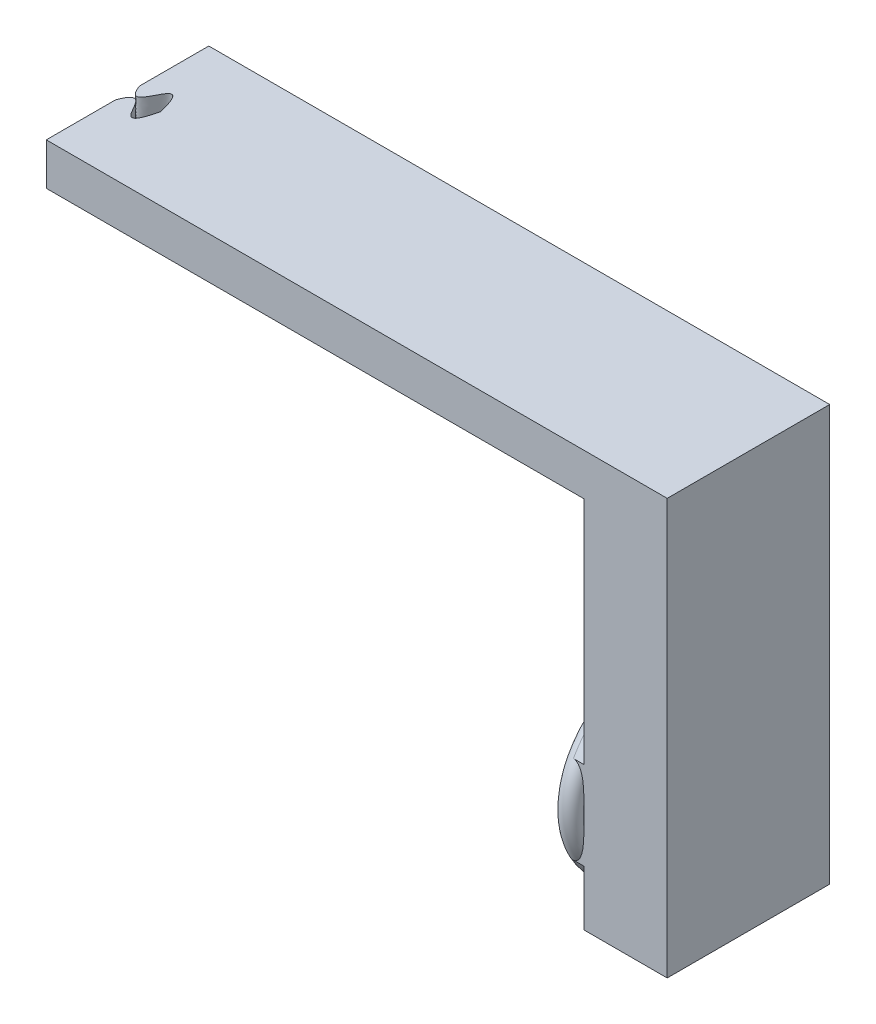
SolidWorks part; units mm, degrees
ref_plane "Front Plane" through (0, 0, 0) normal (0, 0, 1) x (1, 0, 0)
ref_plane "Top Plane" through (0, 0, 0) normal (0, 1, 0) x (1, 0, 0)
ref_plane "Right Plane" through (0, 0, 0) normal (1, 0, 0) x (0, 0, -1)
sketch "Sketch1" plane through (0, 0, 0) normal (0, 1, 0) x (1, 0, 0)
  line L0 (0, 22.1828) -> (0, 38.695)
  line L1 (0, 0) -> (147.8309, 0)
  line L2 (0, 0) -> (0, 16.5121)
  line L3 (0, 38.695) -> (147.8309, 38.695)
  line L4 (147.8309, 0) -> (147.8309, 38.695)
  spline S0 degree 3 poles (0, 22.1828) (3.3888, 13.1405) (4.5622, 33.0605) (7.8124, 19.3475) knots 0 0 0 0 1 1 1 1
  spline S1 degree 3 poles (0, 16.5121) (3.3888, 25.5545) (4.7666, 6.6353) (7.8124, 19.3475) knots 0 0 0 0 1 1 1 1
  point P7 (0, 0)
  point P8 (7.768, 18.8969)
  point P9 (0, 0)
  point P12 (0, 0)
  point P13 (0, 0)
  point P14 (0, 0)
  point P15 (7.8124, 19.3475)
  point P16 (0, 0)
extrude "Boss-Extrude1" add sketch "Sketch1" along normal blind 10
sketch "Sketch5" plane through (0, 0, 0) normal (0, -1, 0) x (1, 0, 0)
  line L0 (0, 0) -> (147.8309, 0) construction
  line L1 (147.8309, -38.695) -> (127.9987, -38.695)
  line L2 (147.8309, -38.695) -> (147.8309, 0)
  line L3 (147.8309, 0) -> (127.9987, 0)
  line L4 (127.9987, -38.695) -> (127.9987, 0)
extrude "Boss-Extrude2" add sketch "Sketch5" along normal blind 88.9
sketch "Sketch6" plane through (127.9987, 0, 0) normal (-1, 0, 0) x (0, 0, 1)
  circle A0 centre (-19.3475, -65.278) radius 18.35
  circle A1 centre (-19.3475, -65.278) radius 22
extrude "Boss-Extrude5" add sketch "Sketch6" along normal blind 5
fillet "Fillet8" radius 2.5 2 edges at (122.9987, -65.278, 2.6525) (127.9987, -65.278, 2.6525)
fillet "Fillet10" radius 2.5 1 edges at (127.9987, -65.278, -41.3475)
